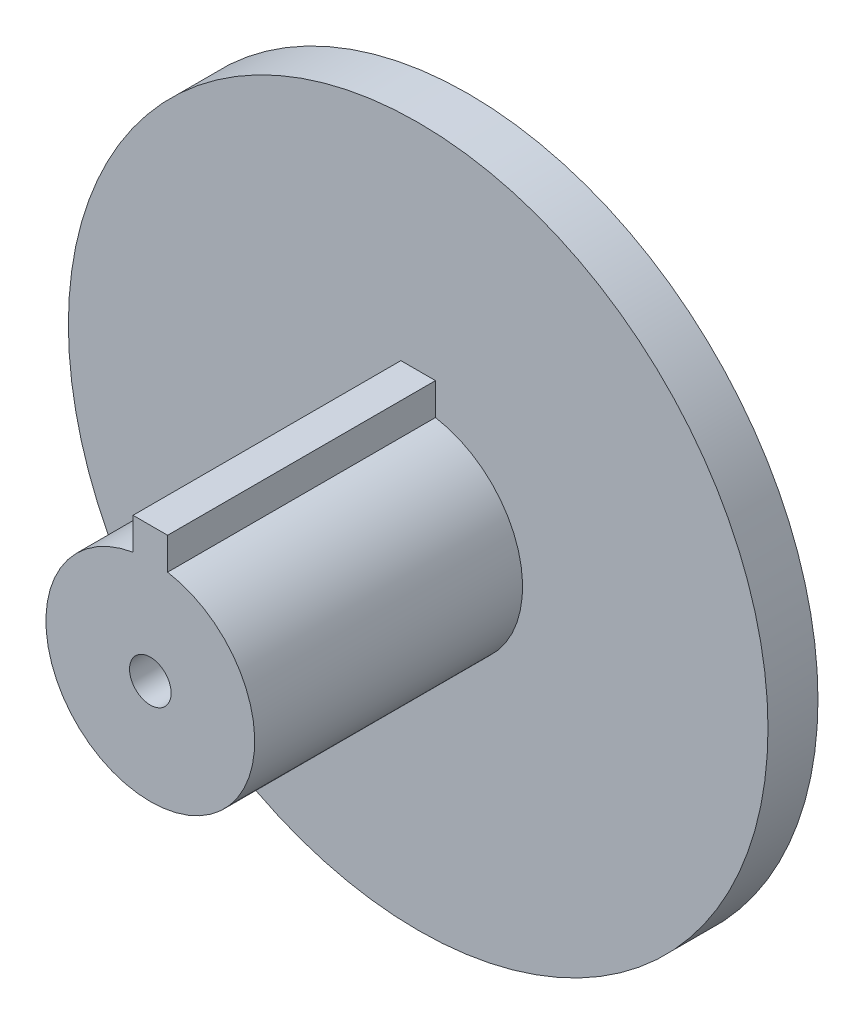
SolidWorks part; units mm, degrees
ref_plane "Front Plane" through (0, 0, 0) normal (0, 0, 1) x (1, 0, 0)
ref_plane "Top Plane" through (0, 0, 0) normal (0, 1, 0) x (1, 0, 0)
ref_plane "Right Plane" through (0, 0, 0) normal (1, 0, 0) x (0, 0, -1)
sketch "Sketch1" plane through (0, 0, 0) normal (0, 0, 1) x (1, 0, 0)
  circle A0 centre (0, 0) radius 44.45
  dimension "D1" = 88.9
extrude "Boss-Extrude1" add sketch "Sketch1" along normal blind 6.35 contours A0
sketch "Sketch2" plane through (0, 0, 6.35) normal (0, 0, 1) x (1, 0, 0)
  line L0 (0, 17.145) -> (0, 13.5382) construction
  line L1 (-2.1971, 17.145) -> (2.1971, 17.145)
  line L2 (-2.1971, 17.145) -> (-2.1971, 13.081)
  line L4 (2.1971, 17.145) -> (2.1971, 13.081)
  arc A1 (-2.1971, 13.081) -> (2.1971, 13.081) centre (0, 0) ccw
  dimension "D1" = 17.145
  dimension "D2" = 0
  dimension "D4" = 4.064
  dimension "D5" = 4.3942
extrude "Boss-Extrude4" add sketch "Sketch2" along normal blind 34.036 contours L2 A1 L4 L1 region at (0, 0.461, 6.35)
sketch "Sketch3" plane through (0, 0, 0) normal (0, 0, -1) x (-1, 0, 0)
  circle A0 centre (0, 0) radius 2.6416
  dimension "D1" = 5.2832
extrude "Cut-Extrude1" cut sketch "Sketch3" against normal through all
equation "\"width_of_film\"= 1.5'a lil more than 35mm"
